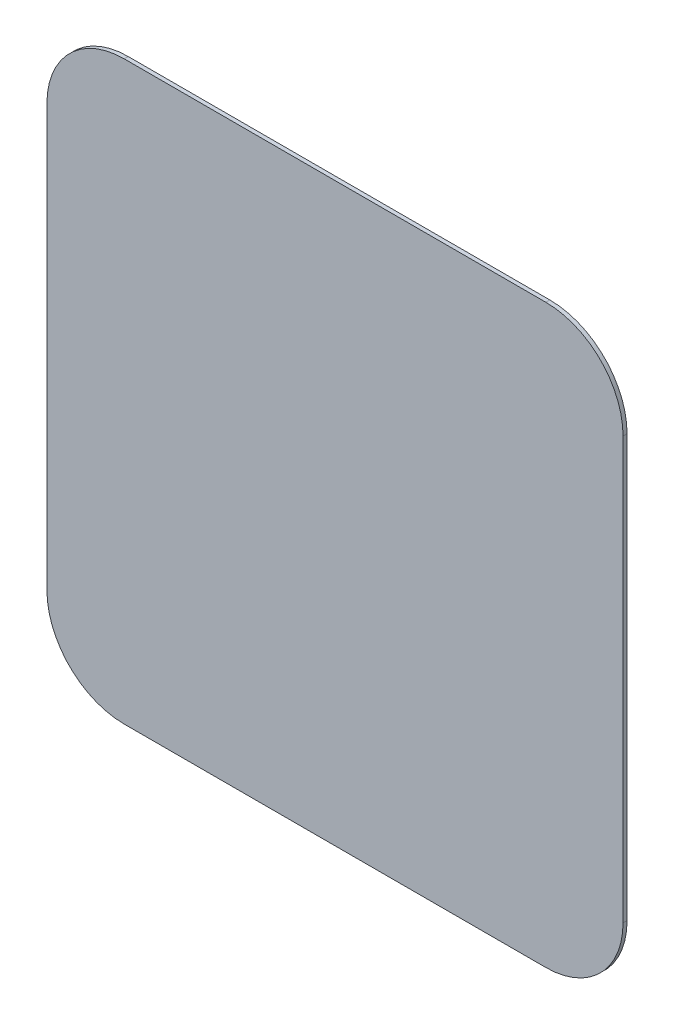
SolidWorks part; units mm, degrees
ref_plane "Ebene vorne" through (0, 0, 0) normal (0, 0, 1) x (1, 0, 0)
ref_plane "Ebene oben" through (0, 0, 0) normal (0, 1, 0) x (1, 0, 0)
ref_plane "Ebene rechts" through (0, 0, 0) normal (1, 0, 0) x (0, 0, -1)
sketch "Skizze1" plane through (0, 0, 0) normal (0, 0, 1) x (1, 0, 0)
  line L0 (-14.35, 10.5) -> (-14.35, -10.5)
  line L1 (10.5, 15) -> (-10.5, 15)
  line L2 (15, 10.5) -> (15, -10.5)
  line L3 (10.5, -15) -> (-10.5, -15)
  line L4 (-15, 10.5) -> (-15, -10.5)
  line L5 (15, 15) -> (-15, -15) construction
  line L6 (15, -15) -> (-15, 15) construction
  line L7 (10.5, -14.35) -> (-10.5, -14.35)
  line L8 (14.35, 10.5) -> (14.35, -10.5)
  line L9 (10.5, 14.35) -> (-10.5, 14.35)
  arc A0 (-10.5, -15) -> (-15, -10.5) centre (-10.5, -10.5) cw
  arc A1 (15, -10.5) -> (10.5, -15) centre (10.5, -10.5) cw
  arc A2 (10.5, 15) -> (15, 10.5) centre (10.5, 10.5) cw
  arc A3 (-10.5, 15) -> (-15, 10.5) centre (-10.5, 10.5) ccw
  arc A4 (-10.5, -14.35) -> (-14.35, -10.5) centre (-10.5, -10.5) cw
  arc A5 (14.35, -10.5) -> (10.5, -14.35) centre (10.5, -10.5) cw
  arc A6 (10.5, 14.35) -> (14.35, 10.5) centre (10.5, 10.5) cw
  arc A7 (-10.5, 14.35) -> (-14.35, 10.5) centre (-10.5, 10.5) ccw
  point P0 (0, 0)
  dimension "D3" = 4.5
  dimension "D1" = 30
  dimension "D2" = 30
  dimension "D4" = 0.65
extrude "Aufsatz-Linear austragen1" add sketch "Skizze1" along normal blind 0.2 contours L9 A7 L0 A4 L7 A5 L8 A6 region at (0, 0, 0)
